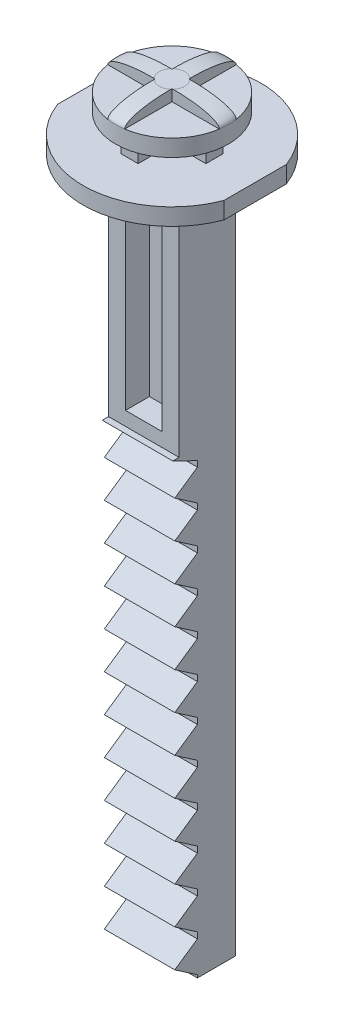
SolidWorks part; units mm, degrees
ref_plane "Front Plane" through (0, 0, 0) normal (0, 0, 1) x (1, 0, 0)
ref_plane "Top Plane" through (0, 0, 0) normal (0, 1, 0) x (1, 0, 0)
ref_plane "Right Plane" through (0, 0, 0) normal (1, 0, 0) x (0, 0, -1)
sketch "Sketch1" plane through (0, 0, 0) normal (0, 1, 0) x (1, 0, 0)
  circle A0 centre (0, 0) radius 6.3
  dimension "D1" = 12.6
extrude "Boss-Extrude1" add sketch "Sketch1" along normal blind 1.2
sketch "Sketch2" plane through (0, 1.2, 0) normal (0, 1, 0) x (1, 0, 0)
  line L1 (0.6, -3) -> (-0.6, -3)
  line L2 (0.6, -3) -> (0.6, 3)
  line L3 (0.6, 3) -> (-0.6, 3)
  line L4 (-0.6, -3) -> (-0.6, 3)
  line L5 (0.6, -3) -> (-0.6, 3) construction
  line L6 (0.6, 3) -> (-0.6, -3) construction
  line L7 (3, -0.6) -> (-3, -0.6)
  line L8 (3, -0.6) -> (3, 0.6)
  line L9 (3, 0.6) -> (-3, 0.6)
  line L10 (-3, -0.6) -> (-3, 0.6)
  line L11 (3, -0.6) -> (-3, 0.6) construction
  line L12 (3, 0.6) -> (-3, -0.6) construction
  point P0 (0, 0)
  point P6 (0, 0)
  dimension "D1" = 1.2
  dimension "D2" = 6
extrude "Boss-Extrude2" add sketch "Sketch2" along normal blind 1.4 contours L2 L3 L4 L1 | L7 L10 L9 L8
sketch "Sketch3" plane through (0, 2.6, 0) normal (0, 1, 0) x (1, 0, 0)
  circle A0 centre (0, 0) radius 4
  dimension "D1" = 8
extrude "Boss-Extrude3" add sketch "Sketch3" along normal blind 1.2
sketch "Sketch4" plane through (0, 3.8, 0) normal (0, 1, 0) x (1, 0, 0)
  line L1 (0.6, -4) -> (-0.6, -4)
  line L2 (0.6, -4) -> (0.6, 4)
  line L3 (0.6, 4) -> (-0.6, 4)
  line L4 (-0.6, -4) -> (-0.6, 4)
  line L5 (0.6, -4) -> (-0.6, 4) construction
  line L6 (0.6, 4) -> (-0.6, -4) construction
  line L7 (4, -0.6) -> (-4, -0.6)
  line L8 (4, -0.6) -> (4, 0.6)
  line L9 (4, 0.6) -> (-4, 0.6)
  line L10 (-4, -0.6) -> (-4, 0.6)
  line L11 (4, -0.6) -> (-4, 0.6) construction
  line L12 (4, 0.6) -> (-4, -0.6) construction
  circle A0 centre (0, 0) radius 4 construction
  point P0 (0, 0)
  point P8 (0, 0)
  circle M8 centre (0, 0) radius 4
  dimension "D1" = 1.2
extrude "Boss-Extrude4" add sketch "Sketch4" along normal blind 0.8 contours L9 L2 L7 M8 | L2 L9 L4 L7 | L2 L7 L4 M8 | L4 L9 L7 M8 | L9 L2 L4 M8 region at (0, 3.8, 2.2925) region at (0, 3.8, 0) region at (2.2925, 3.8, 0) region at (-2.2925, 3.8, 0) region at (0, 3.8, -2.2925)
fillet "Fillet1" radius 0.8 4 edges at (0, 4.6, 4) (-4, 4.6, 0) (4, 4.6, 0) (0, 4.6, -4) second distance 3.1 first distance on face at (0, 4.2, 0)
sketch "Sketch5" plane through (0, 0, 0) normal (0, -1, 0) x (-1, 0, 0)
  line L1 (-5.9, 5.9) -> (5.9, 5.9) construction
  line L2 (-5.9, 5.9) -> (-5.9, -5.9) construction
  line L3 (-5.9, -5.9) -> (5.9, -5.9) construction
  line L4 (5.9, 5.9) -> (5.9, -5.9) construction
  line L5 (-5.9, 5.9) -> (5.9, -5.9) construction
  line L6 (-5.9, -5.9) -> (5.9, 5.9) construction
  line L7 (5.9, -5.9) -> (6.9, -5.9)
  line L8 (5.9, -5.9) -> (5.9, 5.9)
  line L9 (5.9, 5.9) -> (6.9, 5.9)
  line L10 (6.9, -5.9) -> (6.9, 5.9)
  line L11 (-5.9, -5.9) -> (-6.9, -5.9)
  line L12 (-5.9, -5.9) -> (-5.9, 5.9)
  line L13 (-5.9, 5.9) -> (-6.9, 5.9)
  line L14 (-6.9, -5.9) -> (-6.9, 5.9)
  point P0 (0, 0)
  dimension "D1" = 11.8
  dimension "D2" = 1
extrude "Cut-Extrude1" cut sketch "Sketch5" against normal up to surface (1.2 mm away) up to face at (0, 1.2, 6.3)
sketch "Sketch6" plane through (0, 0, 0) normal (0, -1, 0) x (-1, 0, 0)
  line L1 (-2.5, 2) -> (2.5, 2)
  line L2 (-2.5, 2) -> (-2.5, -2)
  line L3 (-2.5, -2) -> (2.5, -2)
  line L4 (2.5, 2) -> (2.5, -2)
  line L5 (-2.5, 2) -> (2.5, -2) construction
  line L6 (-2.5, -2) -> (2.5, 2) construction
  point P0 (0, 0)
  dimension "D1" = 5
  dimension "D2" = 4
extrude "Boss-Extrude5" add sketch "Sketch6" along normal blind 49
sketch "Sketch7" plane through (0, 0, 2) normal (0, 0, 1) x (1, 0, 0)
  line L0 (2.5, 0) -> (-2.5, 0) construction
  line L1 (-1.3, 0) -> (1.3, 0)
  line L2 (-1.3, 0) -> (-1.3, -15.4)
  line L3 (-1.3, -15.4) -> (1.3, -15.4)
  line L4 (1.3, 0) -> (1.3, -15.4)
  line L6 (0, 0) -> (0, 50000) construction
  line L7 (5.9, 1.2) -> (-5.9, 1.2) construction
  point P13 (0, 1.2)
  dimension "D1" = 15.4
  dimension "D2" = 2.6
extrude "Cut-Extrude2" cut sketch "Sketch7" against normal blind 1.7
sketch "Sketch8" plane through (0, 0, -2) normal (0, 0, -1) x (-1, 0, 0)
  line L0 (2.5, 0) -> (-2.5, 0) construction
  line L1 (-1.3, 0) -> (1.3, 0)
  line L2 (-1.3, 0) -> (-1.3, -12.6)
  line L3 (-1.3, -12.6) -> (1.3, -12.6)
  line L4 (1.3, 0) -> (1.3, -12.6)
  line L5 (0, 0) -> (0, 50000) construction
  line L6 (5.9, 1.2) -> (-5.9, 1.2) construction
  line L9 (2.5, -49) -> (-2.5, -49) construction
  line L10 (-1.3, -12.6) -> (1.3, -12.6) construction
  line L11 (-1.3, -12.6) -> (-1.3, -13.8) construction
  line L12 (-1.3, -13.8) -> (1.3, -13.8) construction
  line L13 (1.3, -12.6) -> (1.3, -13.8) construction
  line L14 (-1.3, -13.8) -> (1.3, -13.8)
  line L15 (-1.3, -13.8) -> (-1.3, -49)
  line L16 (-1.3, -49) -> (1.3, -49)
  line L17 (1.3, -13.8) -> (1.3, -49)
  point P11 (0, 1.2)
  line M2 (2.5, 0) -> (-2.5, 0)
  line M4 (-2.5, -49) -> (2.5, -49)
  dimension "D1" = 2.6
  dimension "D2" = 12.6
  dimension "D3" = 1.2
extrude "Cut-Extrude3" cut sketch "Sketch8" against normal blind 1.2 contours L4 L2 L3 M2 | L17 L14 L15 M4 region at (0, -6.3, -2) region at (0, -31.4, -2)
ref_plane "Plane1" through (0, -12.6, 0) normal (0, 1, 0) x (1, 0, 0)
sketch "Sketch12" plane through (0, -12.6, 0) normal (0, 1, 0) x (1, 0, 0)
  line L2 (-2.5, 2) -> (2.5, 2) construction
  line L3 (-2.5, 2) -> (-2.5, 2.8) construction
  line L4 (-2.5, 2.8) -> (2.5, 2.8) construction
  line L5 (2.5, 2) -> (2.5, 2.8) construction
  line L13 (-1.3, 2) -> (-2.5, 2)
  line L14 (-1.3, 0.8) -> (-1.3, 2)
  line L15 (1.3, 0.8) -> (-1.3, 0.8)
  line L16 (1.3, 2) -> (1.3, 0.8)
  line L17 (2.5, 2) -> (1.3, 2)
  line L18 (2.5, -2) -> (2.5, 2)
  line L19 (-2.5, -2) -> (2.5, -2)
  line L20 (-2.5, 2) -> (-2.5, -2)
  line L21 (-1.3, 2) -> (-2.5, 2)
  line L22 (-1.3, 0.8) -> (-1.3, 2)
  line L23 (1.3, 0.8) -> (-1.3, 0.8)
  line L24 (1.3, 2) -> (1.3, 0.8)
  line L25 (2.5, 2) -> (1.3, 2)
  arc A0 (-2.5, 2) -> (2.5, 2) centre (0, -1.5062) cw
  dimension "D1" = 0.8
  dimension "D2" = 0
extrude "Boss-Extrude6" add sketch "Sketch12" against normal blind 1.2
sketch "Sketch13" plane through (0, 0, 2) normal (0, 0, 1) x (1, 0, 0)
  line L0 (1.3, -15.4) -> (1.3, 0) construction
  line L1 (-1.3, -15.4) -> (1.3, -15.4) construction
  line L2 (-1.3, -15.4) -> (-1.3, -16.6) construction
  line L3 (-1.3, -16.6) -> (1.3, -16.6) construction
  line L4 (1.3, -15.4) -> (1.3, -16.6) construction
  line L5 (-2.5, -49) -> (-2.5, 0) construction
  line L6 (-2.5, -16.6) -> (2.5, -16.6)
  line L7 (-2.5, -16.6) -> (-2.5, -49)
  line L8 (-2.5, -49) -> (2.5, -49)
  line L9 (2.5, -16.6) -> (2.5, -49)
  line L10 (2.5, -49) -> (2.5, 0) construction
  line L11 (2.5, -49) -> (-2.5, -49) construction
  dimension "D1" = 1.2
extrude "Cut-Extrude4" cut sketch "Sketch13" against normal blind 1.3
ref_plane "Plane2" through (2.5, 0, 0) normal (1, 0, 0) x (0, 0, -1)
sketch "Sketch14" plane through (2.5, 0, 0) normal (1, 0, 0) x (0, 0, -1)
  line L0 (-0.7, -46.6) -> (-0.7, -48.8)
  line L1 (-0.7, -49) -> (-0.7, -16.6) construction
  line L2 (-0.7, -48.8) -> (-2.3, -47.7)
  line L3 (-2.3, -47.7) -> (-0.7, -46.6)
  line L4 (2, -49) -> (-0.7, -49) construction
  line L38 (-2.3, -45.0669) -> (-0.7, -43.9669)
  line L39 (-0.7, -43.9669) -> (-0.7, -46.1669)
  line L40 (-0.7, -46.1669) -> (-2.3, -45.0669)
  line L41 (-2.3, -42.4339) -> (-0.7, -41.3339)
  line L42 (-0.7, -41.3339) -> (-0.7, -43.5339)
  line L43 (-0.7, -43.5339) -> (-2.3, -42.4339)
  line L44 (-2.3, -39.8008) -> (-0.7, -38.7008)
  line L45 (-0.7, -38.7008) -> (-0.7, -40.9008)
  line L46 (-0.7, -40.9008) -> (-2.3, -39.8008)
  line L47 (-2.3, -37.1677) -> (-0.7, -36.0677)
  line L48 (-0.7, -36.0677) -> (-0.7, -38.2677)
  line L49 (-0.7, -38.2677) -> (-2.3, -37.1677)
  line L50 (-2.3, -34.5347) -> (-0.7, -33.4347)
  line L51 (-0.7, -33.4347) -> (-0.7, -35.6347)
  line L52 (-0.7, -35.6347) -> (-2.3, -34.5347)
  line L53 (-2.3, -31.9016) -> (-0.7, -30.8016)
  line L54 (-0.7, -30.8016) -> (-0.7, -33.0016)
  line L55 (-0.7, -33.0016) -> (-2.3, -31.9016)
  line L56 (-2.3, -29.2685) -> (-0.7, -28.1685)
  line L57 (-0.7, -28.1685) -> (-0.7, -30.3685)
  line L58 (-0.7, -30.3685) -> (-2.3, -29.2685)
  line L59 (-2.3, -26.6355) -> (-0.7, -25.5355)
  line L60 (-0.7, -25.5355) -> (-0.7, -27.7355)
  line L61 (-0.7, -27.7355) -> (-2.3, -26.6355)
  line L62 (-2.3, -24.0024) -> (-0.7, -22.9024)
  line L63 (-0.7, -22.9024) -> (-0.7, -25.1024)
  line L64 (-0.7, -25.1024) -> (-2.3, -24.0024)
  line L65 (-2.3, -21.3693) -> (-0.7, -20.2693)
  line L66 (-0.7, -20.2693) -> (-0.7, -22.4693)
  line L67 (-0.7, -22.4693) -> (-2.3, -21.3693)
  line L68 (-2.3, -18.7363) -> (-0.7, -17.6363)
  line L69 (-0.7, -17.6363) -> (-0.7, -19.8363)
  line L70 (-0.7, -19.8363) -> (-2.3, -18.7363)
  line L71 (-0.7, -17.2363) -> (-2.444, -16.3827)
  line L72 (-0.7, -17.6363) -> (-2.3, -17.6363) construction
  line L73 (-0.7, -17.6363) -> (-0.7, -17.2363) construction
  line L74 (-0.7, -17.2363) -> (-2.3, -17.2363) construction
  line L75 (-2.3, -17.6363) -> (-2.3, -17.2363) construction
  line L76 (-2.444, -16.3827) -> (-0.7, -16.3827)
  line L77 (-0.7, -17.2363) -> (-0.7, -16.3827)
  point P45 (0, 0)
  dimension "D1" = 1.6
  dimension "D2" = 2.2
  dimension "D3" = 0.2
  dimension "D5" = 0.4
  dimension "D6" = 1.6
  dimension "D4" = 12
extrude "Boss-Extrude7" add sketch "Sketch14" against normal blind 5
